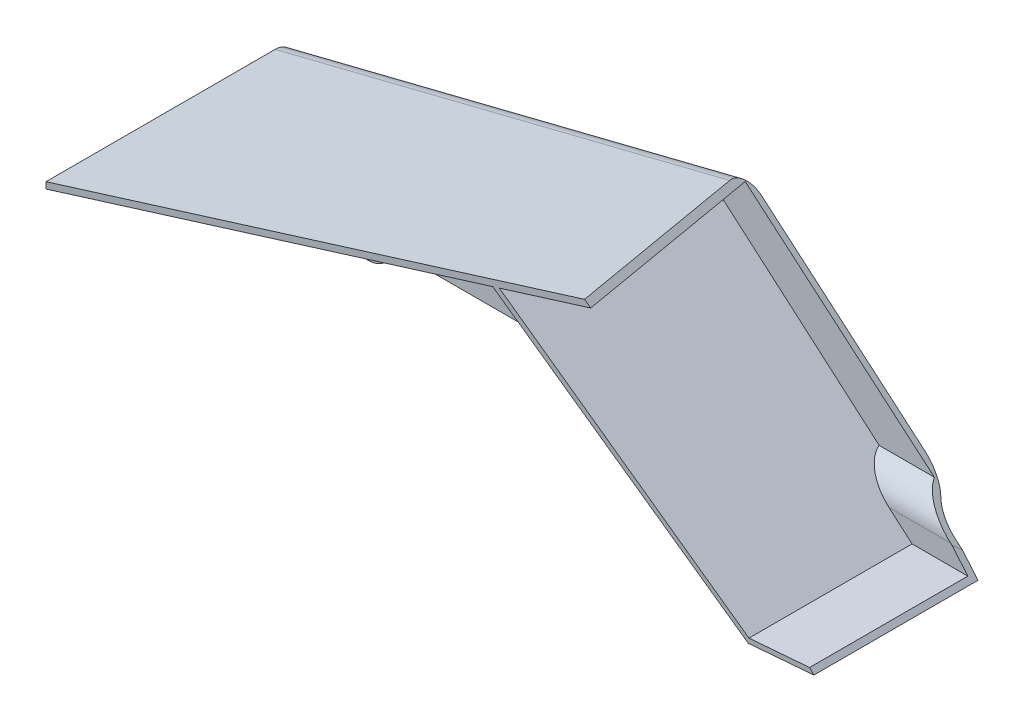
SolidWorks part; units mm, degrees
ref_plane "Piano frontale" through (0, 0, 0) normal (0, 0, 1) x (1, 0, 0)
ref_plane "Piano superiore" through (0, 0, 0) normal (0, 1, 0) x (1, 0, 0)
ref_plane "Piano destro" through (0, 0, 0) normal (1, 0, 0) x (0, 0, -1)
sketch "Schizzo1" plane through (0, 0, 0) normal (0, 0, 1) x (1, 0, 0)
  line L0 (-49, 0) -> (49, 0)
  line L1 (-49, 0) -> (-49, 5)
  line L2 (-49, 5) -> (-65, 5)
  line L3 (-65, 5) -> (-65, 17)
  line L4 (-65, 17) -> (17.4553, 37.6429)
  line L5 (17.4553, 37.6429) -> (49, 0)
  point P4 (0, 0)
  point P8 (2.9043, 34)
  dimension "D1" = 98
  dimension "D2" = 5
  dimension "D3" = 16
  dimension "D4" = 12
  dimension "D5" = 85
  dimension "D6" = 70
  dimension "D7" = 34
extrude "Estrusione-Estrusione1" add sketch "Schizzo1" along normal blind 40
sketch "Schizzo3" plane through (0, 0, 0) normal (1, 0, 0) x (0, 0, -1)
  line L0 (-3.5, 4) -> (-3.5, 0)
  line L1 (-40, 0) -> (0, 0) construction
  line L2 (-3.5, 0) -> (0, 0)
  line L3 (0, 0) -> (0, 0.5)
  line L4 (0, 0.5) -> (0, 7.5)
  arc A0 (0, 7.5) -> (-3.5, 4) centre (0, 4) ccw
  dimension "D1" = 7
  dimension "D2" = 4
extrude "Taglio-Estrusione1" cut sketch "Schizzo3" against normal through all both and the other way through all
shell "Svuota1" thickness 1 removed face at (0, 0, 21.75) removed face at (-49, 2.8011, 18.0781) removed face at (-57, 5, 21.6771) removed face at (-65, 10.4112, 16.7537) removed face at (-26.9241, 10.7738, 40) removed face at (36.7777, 14.5851, 14.6208)
sketch "Schizzo5" plane through (0, 0, 0) normal (0, 0, 1) x (1, 0, 0)
  line L0 (1.3224, 32.5731) -> (2.2925, 32.816)
  line L1 (18.1693, 36.7908) -> (-65, 15.9691) construction
  line L2 (2.2925, 32.816) -> (39.3577, 0.7665)
  line L3 (39.3577, 0.7665) -> (48.3577, 0.7665)
  line L4 (49, 0) -> (45.648, 4) construction
  line L5 (48.3577, 0.7665) -> (49, 0)
  line L6 (49, 0) -> (39.2565, 0)
  line L7 (-49, 0) -> (49, 0) construction
  line L8 (39.2565, 0) -> (1.3224, 32.5731)
  dimension "D1" = 1
  dimension "D2" = 1
  dimension "D3" = 49
  dimension "D4" = 50
  dimension "D5" = 9
extrude "Estrusione-Estrusione2" add sketch "Schizzo5" against normal up to body from surface separate body starting at face at (-23.5938, 26.8507, 40)
sketch "Schizzo8" plane through (0, 0, 0) normal (0, 0, 1) x (1, 0, 0)
  line L0 (-49, 4) -> (-49, 0) construction
  line L1 (-49, 0) -> (39.2565, 0) construction
  circle A0 centre (-45, 4) radius 4
  circle A1 centre (9, 4) radius 4
  dimension "D1" = 8
  dimension "D2" = 54
extrude "Estrusione-Estrusione3" add sketch "Schizzo8" against normal up to body from offset 8 separate body
sketch "Schizzo9" plane through (0, 0, 0) normal (0, 0, 1) x (1, 0, 0)
  circle A0 centre (-45, 4) radius 1.5
  circle A1 centre (9, 4) radius 1.5
  arc A2 (-49, 4) -> (-45, 0) centre (-45, 4) ccw construction
  dimension "D1" = 3
extrude "Taglio-Estrusione2" cut sketch "Schizzo9" against normal blind 30 from surface starting at face at (-41, 4, 8)
ref_plane "Piano1" through (-7.8386, 31.3105, 0) normal (-0.2429, 0.9701, 0) x (0.9701, 0.2429, 0)
sketch "Schizzo13" plane through (-7.8386, 31.3105, 0) normal (-0.2429, 0.9701, 0) x (0.9701, 0.2429, 0)
  line L1 (26.0745, 0) -> (-58.9255, 0) construction
  line L2 (16.0745, 0) -> (26.0745, 0)
  line L3 (26.0745, 0) -> (26.0745, -40)
  line L4 (26.0745, -40) -> (25.0745, -40)
  line L5 (26.0745, -40) -> (-58.9255, -40) construction
  line L6 (25.0745, -40) -> (16.0745, 0)
  dimension "D1" = 10
  dimension "D2" = 1
sketch "Schizzo17" plane through (0, 0, 0) normal (0, 0, 1) x (1, 0, 0)
  line L0 (7.7547, 35.2143) -> (60.9911, -10.2377)
  line L8 (17.4553, 37.6429) -> (-65, 17) construction
  dimension "D1" = 10
  dimension "D2" = 70
sweep "Taglia-Sweep3" cut profiles "Schizzo13" path "Schizzo17"
sketch "Schizzo18" plane through (0, 0, 0) normal (0, 1, 0) x (1, 0, 0)
  line L1 (-1, -3) -> (-12, -3)
  line L2 (-1, -3) -> (-1, -4)
  line L3 (-1, -4) -> (-12, -4)
  line L4 (-12, -3) -> (-12, -4)
  line L5 (5, -4.5) -> (5, -8) construction
  line L6 (-45, -4.5) -> (9, -4.5) construction
  point P6 (-1, -3.5)
  dimension "D1" = 1
  dimension "D2" = 11
  dimension "D3" = 6
  dimension "D4" = 0.5
extrude "Taglio-Estrusione3" cut sketch "Schizzo18" along normal blind 5
fillet "Raccordo1" radius 2 1 edges at (16.952, 37.0014, 40) type face fillet first side face at (31.2304, 17.569, 9.9493) second side face at (8.3491, 17.3894, 40)
fillet "Raccordo2" radius 3 1 edges at (-28.6227, 26.1071, 0) type face fillet first side face at (-18.398, 28.6669, 23.62) second side face at (-20.5075, 16.8036, 0)
fillet "Raccordo3" radius 4 1 edges at (-12.3923, 7.5, 0)
sketch "Schizzo22" plane through (0, 0, 0) normal (0, 1, 0) x (1, 0, 0)
  line L0 (-65, -40) -> (49, -30)
  line L1 (49, -40) -> (49, -3.5) construction
  line L2 (49, -30) -> (49, -40)
  line L4 (13.6272, -40) -> (49, -40)
  line L5 (13.6272, -40) -> (-65, -40) construction
  line L6 (13.6272, -40) -> (-65, -40)
  dimension "D2" = 10
extrude "Taglio-Estrusione4" cut sketch "Schizzo22" against normal blind 10 and the other way through all
